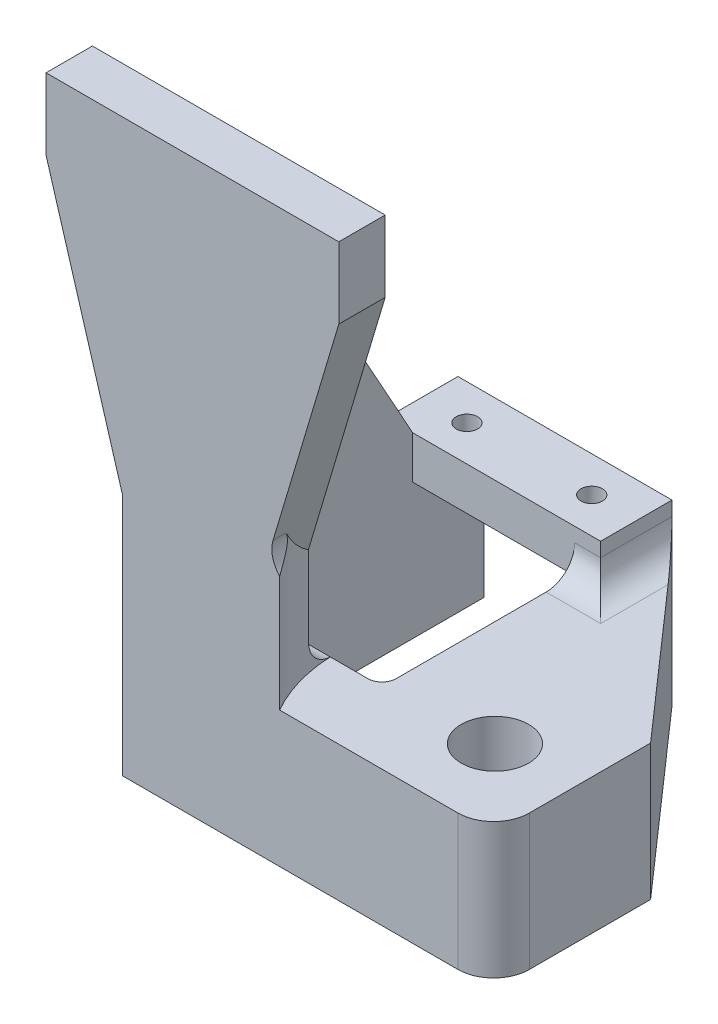
SolidWorks part; units mm, degrees
ref_plane "Front Plane" through (0, 0, 0) normal (0, 0, 1) x (1, 0, 0)
ref_plane "Top Plane" through (0, 0, 0) normal (0, 1, 0) x (1, 0, 0)
ref_plane "Right Plane" through (0, 0, 0) normal (1, 0, 0) x (0, 0, -1)
sketch "Sketch1" plane through (0, 0, 0) normal (0, 1, 0) x (1, 0, 0)
  line L0 (-5.7502, 0) -> (11.7498, 0) construction
  circle A0 centre (-5.7502, 0) radius 1.5 construction
  circle A1 centre (11.7498, 0) radius 1.5 construction
  dimension "D1" = 3
  dimension "D2" = 17.5
sketch "Sketch2" plane through (0, 0, 0) normal (0, 1, 0) x (1, 0, 0)
  line L0 (2.9998, -5) -> (2.9998, 5) construction
  line L1 (-12.0002, -5) -> (17.9998, -5)
  line L2 (-12.0002, -5) -> (-12.0002, 5)
  line L3 (-12.0002, 5) -> (17.9998, 5)
  line L4 (17.9998, -5) -> (17.9998, 5)
  line L5 (-5.7502, 0) -> (11.7498, 0) construction
  line L6 (-12.0002, 0) -> (17.9998, 0) construction
  point P6 (2.9998, 0)
  point P11 (2.9998, 0)
  dimension "D1" = 30
  dimension "D2" = 10
extrude "Boss-Extrude1" add sketch "Sketch2" along normal blind 25
sketch "Sketch3" plane through (0, 0, 5) normal (0, 0, 1) x (1, 0, 0)
  line L0 (2.9998, 25) -> (2.9998, 0) construction
  line L1 (-12.0002, 25) -> (17.9998, 25) construction
  line L2 (-5.7502, 0) -> (11.7498, 0) construction
  line L3 (-12.0002, 12.5) -> (17.9998, 12.5) construction
  line L4 (-12.0002, 25) -> (-12.0002, 0) construction
  line L5 (17.9998, 25) -> (17.9998, 0) construction
  line L6 (-12.0002, 0) -> (17.9998, 0) construction
  line L7 (-8.3502, 0) -> (14.3498, 0)
  line L8 (-8.3502, 0) -> (-8.3502, 19)
  line L9 (-8.3502, 19) -> (14.3498, 19)
  line L10 (14.3498, 0) -> (14.3498, 19)
  line L11 (-8.3502, 0) -> (14.3498, 19) construction
  line L12 (-8.3502, 19) -> (14.3498, 0) construction
  point P12 (2.9998, 12.5)
  dimension "D1" = 19
  dimension "D2" = 22.7
extrude "Cut-Extrude1" cut sketch "Sketch3" against normal through all
sketch "Sketch4" plane through (0, 0, 0) normal (0, -1, 0) x (1, 0, 0)
  circle A0 centre (-5.7502, 0) radius 1.5
  circle A1 centre (11.7498, 0) radius 1.5
extrude "Cut-Extrude2" cut sketch "Sketch4" against normal through all
sketch "Sketch5" plane through (0, 0, 5) normal (0, 0, 1) x (1, 0, 0)
  line L0 (13.2498, 0) -> (10.2498, 0) construction
  line L1 (17.9998, 19) -> (14.3498, 19)
  line L2 (17.9998, 19) -> (17.9998, 0)
  line L3 (17.9998, 0) -> (14.3498, 0)
  line L4 (14.3498, 19) -> (14.3498, 0)
  line L5 (14.3498, 0) -> (14.3498, 19) construction
  line L6 (14.3498, 19) -> (-8.3502, 19) construction
extrude "Boss-Extrude2" add sketch "Sketch5" along normal blind 37
sketch "Sketch6" plane through (0, 0, 5) normal (0, 0, 1) x (1, 0, 0)
  line L0 (-8.3502, 19) -> (-8.3502, 0) construction
  line L1 (-12.0002, 0) -> (-8.3502, 0)
  line L2 (-12.0002, 0) -> (-12.0002, 19)
  line L3 (-12.0002, 19) -> (-8.3502, 19)
  line L4 (-8.3502, 0) -> (-8.3502, 19)
  line L6 (14.3498, 19) -> (-8.3502, 19) construction
extrude "Boss-Extrude3" add sketch "Sketch6" along normal blind 37
sketch "Sketch11" plane through (14.3498, 0, 0) normal (-1, 0, 0) x (0, 0, 1)
  line L0 (42, 19) -> (5, 19) construction
  line L1 (42, 0) -> (32, 0)
  line L2 (42, 0) -> (42, 19)
  line L3 (42, 19) -> (32, 19)
  line L4 (32, 0) -> (32, 19)
  dimension "D1" = 10
extrude "Boss-Extrude7" add sketch "Sketch11" along normal up to surface (22.7 mm away) up to face at (-8.3502, 11.4, 15.8)
sketch "Sketch12" plane through (0, 0, 0) normal (0, -1, 0) x (1, 0, 0)
  line L0 (-8.3502, 32) -> (14.3498, 32) construction
  line L1 (0.3998, 32) -> (5.5998, 32)
  line L2 (0.3998, 32) -> (0.3998, 37.2)
  line L3 (0.3998, 37.2) -> (5.5998, 37.2)
  line L4 (5.5998, 32) -> (5.5998, 37.2)
  line L5 (0.3998, 34.6) -> (-8.3502, 34.6) construction
  line L6 (-8.3502, 34.6) -> (-8.3502, 32) construction
  line L7 (5.5998, 34.6) -> (14.3498, 34.6) construction
  line L8 (14.3498, 34.6) -> (14.3498, 32) construction
  dimension "D1" = 5.2
  dimension "D2" = 5.2
extrude "Cut-Extrude4" cut sketch "Sketch12" against normal blind 11.1
sketch "Sketch13" plane through (0, 11.1, 0) normal (0, -1, 0) x (1, 0, 0)
  line L0 (5.5998, 32) -> (5.5998, 37.2) construction
  line L1 (5.5998, 37.2) -> (0.3998, 37.2) construction
  circle A0 centre (3.0998, 34.7) radius 1.4
  dimension "D3" = 2.8
  dimension "D1" = 2.5
  dimension "D2" = 2.5
extrude "Cut-Extrude5" [suppressed] cut sketch "Sketch13" against normal through all
sketch "Sketch14" plane through (17.9998, 0, 0) normal (1, 0, 0) x (0, 0, -1)
  line L0 (-42, 19) -> (-5, 19) construction
  line L1 (-42, 0) -> (-20, 0)
  line L2 (-42, 0) -> (-42, 19)
  line L3 (-42, 19) -> (-20, 19)
  line L4 (-20, 0) -> (-20, 19)
  dimension "D1" = 22
extrude "Boss-Extrude8" add sketch "Sketch14" along normal blind 22
sketch "Sketch15" plane through (0, 19, 0) normal (0, 1, 0) x (1, 0, 0)
  line L0 (17.9998, -20) -> (17.9998, -42) construction
  line L1 (39.9998, -42) -> (-12.0002, -42) construction
  line L2 (17.9998, -31) -> (39.9998, -31) construction
  line L3 (39.9998, -20) -> (39.9998, -42) construction
  circle A0 centre (29.1798, -31) radius 4.72
  dimension "D1" = 9.44
  dimension "D2" = 11.18
extrude "Cut-Extrude6" cut sketch "Sketch15" against normal through all
sketch "Sketch16" plane through (0, 19, 0) normal (0, 1, 0) x (1, 0, 0)
  line L1 (-12.0002, -42) -> (9.9998, -42)
  line L2 (-12.0002, -42) -> (-12.0002, -35.5)
  line L3 (-12.0002, -35.5) -> (7.5321, -35.5)
  line L5 (39.9998, -42) -> (-12.0002, -42) construction
  line L6 (-8.3502, -32) -> (14.3498, -32) construction
  arc A0 (7.5321, -35.5) -> (9.9998, -42) centre (29.1798, -31) ccw
  circle A1 centre (29.1798, -31) radius 4.72 construction
  point P9 (0, 0)
  point P14 (0, 0)
  point P15 (0, 0)
  dimension "D1" = 22
  dimension "D2" = 3.5
extrude "Boss-Extrude9" add sketch "Sketch16" along normal blind 15
sketch "Sketch18" plane through (0, 19, 0) normal (0, 1, 0) x (1, 0, 0)
  line L0 (17.9998, -20) -> (17.9998, 5)
  line L2 (39.9998, -20) -> (17.9998, -20)
  line L3 (17.9998, 5) -> (39.9998, -20)
extrude "Boss-Extrude11" add sketch "Sketch18" against normal up to surface (19 mm away) up to face at (29.1798, 0, 35.72)
sketch "Sketch19" plane through (0, 0, 42) normal (0, 0, 1) x (1, 0, 0)
  line L1 (-22.7559, 80) -> (18.2878, 80)
  line L2 (18.2878, 80) -> (18.2878, 70)
  line L3 (18.2878, 70) -> (7.5321, 34)
  line L4 (7.5321, 34) -> (-12.0002, 34)
  line L5 (-12.0002, 0) -> (39.9998, 0) construction
  line L6 (-22.7559, 80) -> (-22.7559, 70)
  line L7 (-22.7559, 70) -> (-12.0002, 34)
  line L8 (-22.7559, 70) -> (18.2878, 70) construction
  line L9 (-2.2341, 70) -> (-2.2341, 34) construction
  line L10 (-12.0002, 34) -> (9.9998, 34) construction
  point P11 (0, 0)
  point P13 (-19.4014, 70)
  point P14 (-2.2341, 34)
  point P15 (20.7554, 70)
  point P16 (5.9239, 34)
  dimension "D1" = 80
  dimension "D2" = 10
extrude "Boss-Extrude12" add sketch "Sketch19" against normal up to surface (6.5 mm away) up to face at (-2.2341, 26.5, 35.5)
sketch "Sketch20" plane through (-12.0002, 0, 0) normal (-1, 0, 0) x (0, 0, 1)
  line L0 (5, 25) -> (35.5, 80)
  line L1 (35.5, 80) -> (35.5, 19)
  line L2 (35.5, 19) -> (5, 19)
  line L3 (5, 19) -> (5, 25)
extrude "Boss-Extrude13" add sketch "Sketch20" against normal up to surface (3.65 mm away) up to face at (-8.3502, 11.4, 11.8)
fillet "Fillet1" radius 5 1 edges at (39.9998, 9.5, 42)
fillet "Fillet2" radius 4 4 edges at (-0.4091, 19, 35.5) (16.1748, 19, 5) (17.9998, 19, 0) (-12.0002, 57, 35.5)
fillet "Fillet3" radius 2 2 edges at (-8.3502, 9.5, 32) (14.3498, 9.5, 32)
fillet "Fillet5" radius 4 1 edges at (7.5321, 34, 38.75)
